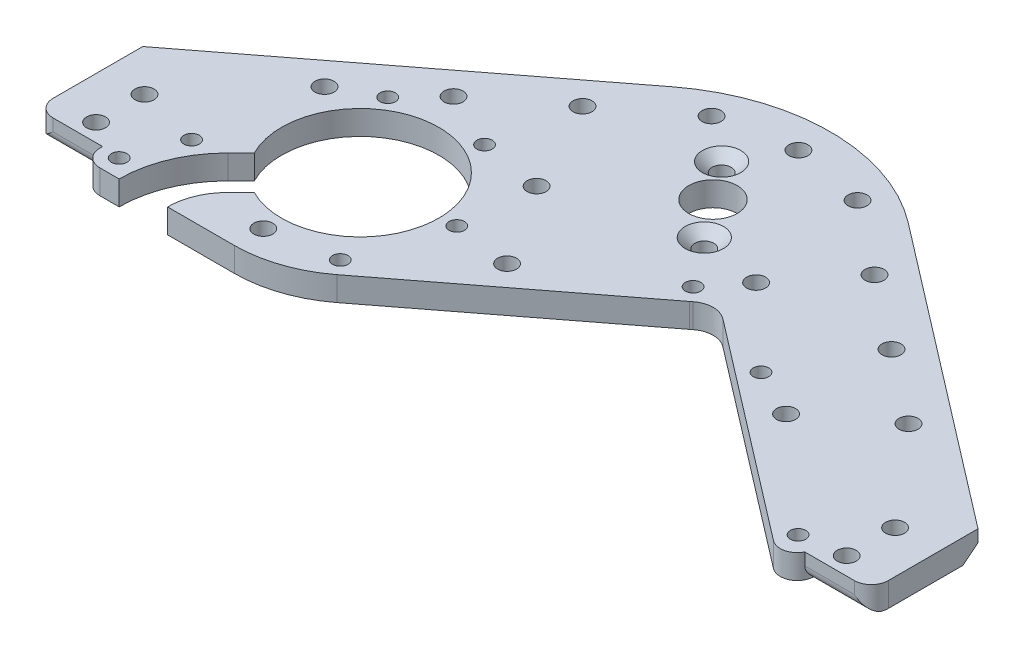
SolidWorks part; units mm, degrees
material "Alum Plate"
ref_plane "Front Plane" through (0, 0, 0) normal (0, 0, 1) x (1, 0, 0)
ref_plane "Top Plane" through (0, 0, 0) normal (0, 1, 0) x (1, 0, 0)
ref_plane "Right Plane" through (0, 0, 0) normal (1, 0, 0) x (0, 0, -1)
sketch "Top Layout" plane through (0, 0, 0) normal (0, 1, 0) x (1, 0, 0)
  line L0 (-114.046, -123.825) -> (-104.775, -123.825) construction
  line L1 (-104.775, -142.875) -> (-101.6, -142.875)
  line L2 (-104.775, -142.875) -> (-104.775, -104.775)
  line L3 (-104.775, -104.775) -> (-101.6, -104.775)
  line L4 (-101.6, -142.875) -> (-101.6, -104.775)
  line L5 (-104.775, -142.875) -> (-101.6, -104.775) construction
  line L6 (-104.775, -104.775) -> (-101.6, -142.875) construction
  line L7 (-19.05, -105.8164) -> (-101.6, -105.8164)
  line L8 (-19.05, -105.8164) -> (-19.05, -141.8336)
  line L9 (-19.05, -141.8336) -> (-101.6, -141.8336)
  line L10 (-101.6, -105.8164) -> (-101.6, -141.8336)
  line L11 (-19.05, -105.8164) -> (-101.6, -141.8336) construction
  line L12 (-19.05, -141.8336) -> (-101.6, -105.8164) construction
  line L13 (-133.096, -85.725) -> (-114.046, -85.725)
  line L14 (-133.096, -85.725) -> (-133.096, -161.925)
  line L15 (-133.096, -161.925) -> (-114.046, -161.925)
  line L16 (-114.046, -85.725) -> (-114.046, -161.925)
  line L17 (-133.096, -85.725) -> (-114.046, -161.925) construction
  line L18 (-133.096, -161.925) -> (-114.046, -85.725) construction
  line L19 (-104.775, -123.825) -> (0, -123.825) construction
  line L20 (0, -123.825) -> (0, 0) construction
  line L21 (-52.3528, -40.1717) -> (0, 0) construction
  line L22 (-70.6449, -16.3328) -> (-18.2922, 23.8388)
  line L23 (-34.0606, -64.0105) -> (18.2922, -23.8388)
  line L24 (-30.9251, 40.3023) -> (-122.2248, -29.7544)
  line L25 (-153.9748, -53.975) -> (-153.9748, -123.825)
  line L26 (-109.5248, -162.052) -> (109.5248, -162.052)
  line L27 (0, -162.052) -> (0, -123.825) construction
  line L28 (-109.5248, -162.052) -> (-109.5248, -20.0093) construction
  line L29 (-104.775, -142.875) -> (-104.775, -152.527)
  line L30 (-104.775, -152.527) -> (104.775, -152.527)
  line L31 (104.775, -104.775) -> (101.6, -104.775)
  line L32 (-144.4498, -73.025) -> (-109.5248, -73.025)
  line L33 (-144.4498, -73.025) -> (-144.4498, -123.825)
  line L34 (-144.4498, -123.825) -> (-109.5248, -123.825) construction
  line L35 (-109.5248, -73.025) -> (-109.5248, -162.052)
  line L36 (-144.4498, -73.025) -> (-109.5248, -123.825) construction
  line L37 (-144.4498, -123.825) -> (-109.5248, -73.025) construction
  line L38 (101.6, -142.875) -> (101.6, -104.775)
  line L39 (104.775, -142.875) -> (101.6, -142.875)
  line L40 (104.775, -142.875) -> (104.775, -104.775)
  line L41 (104.775, -142.875) -> (104.775, -152.527)
  line L42 (109.5248, -162.052) -> (109.5248, -20.0093) construction
  line L43 (30.9251, 40.3023) -> (122.2248, -29.7544)
  line L45 (19.05, -141.8336) -> (101.6, -141.8336)
  line L46 (101.6, -105.8164) -> (101.6, -141.8336)
  line L47 (19.05, -105.8164) -> (101.6, -105.8164)
  line L48 (19.05, -105.8164) -> (19.05, -141.8336)
  line L49 (133.096, -161.925) -> (114.046, -161.925)
  line L50 (114.046, -85.725) -> (114.046, -161.925)
  line L51 (133.096, -85.725) -> (114.046, -85.725)
  line L52 (133.096, -85.725) -> (133.096, -161.925)
  line L53 (144.4498, -123.825) -> (109.5248, -123.825) construction
  line L54 (109.5248, -73.025) -> (109.5248, -162.052)
  line L55 (144.4498, -73.025) -> (109.5248, -73.025)
  line L56 (144.4498, -73.025) -> (144.4498, -123.825)
  line L57 (-109.5248, -123.825) -> (-109.5248, -162.052) construction
  line L62 (-153.9748, -53.975) -> (-122.2248, -53.975)
  line L63 (-122.2248, -53.975) -> (-122.2248, -29.7544)
  line L64 (-144.4498, -123.825) -> (-153.9748, -123.825)
  line L65 (153.9748, -53.975) -> (153.9748, -123.825)
  line L66 (109.5248, -123.825) -> (109.5248, -162.052) construction
  line L67 (144.4498, -123.825) -> (153.9748, -123.825)
  line L68 (122.2248, -29.7544) -> (122.2248, -53.975)
  line L73 (-104.775, -104.775) -> (-104.775, -16.3647) construction
  line L74 (-95.25, -162.052) -> (-95.25, -9.0559) construction
  line L75 (-109.5248, -162.052) -> (-109.5248, -123.825) construction
  line L76 (109.5248, -162.052) -> (109.5248, -123.825) construction
  line L77 (122.2248, -53.975) -> (153.9748, -53.975)
  line L83 (104.775, -155.5496) -> (-104.775, -155.5496) construction
  line L88 (95.25, -162.052) -> (95.25, -9.0559) construction
  line L89 (104.775, -104.775) -> (104.775, -16.3647) construction
  line L92 (-104.775, -152.527) -> (-104.775, -162.052) construction
  line L93 (-14.605, -76.327) -> (14.605, -76.327)
  line L94 (-14.605, -76.327) -> (-14.605, -152.527)
  line L95 (-14.605, -152.527) -> (14.605, -152.527)
  line L96 (14.605, -76.327) -> (14.605, -152.527)
  line L97 (-14.605, -76.327) -> (14.605, -152.527) construction
  line L98 (-14.605, -152.527) -> (14.605, -76.327) construction
  line L99 (104.775, -152.527) -> (104.775, -162.052) construction
  line L100 (-19.05, -105.8164) -> (0, -105.8164) construction
  line L107 (0, -105.8164) -> (19.05, -105.8164) construction
  line L108 (104.775, -123.825) -> (114.046, -123.825) construction
  circle A0 centre (0, 0) radius 114.3
  circle A1 centre (0, 0) radius 6.35
  circle A2 centre (-52.3528, -40.1717) radius 17.8
  circle A3 centre (0, 0) radius 30.0482
  circle A4 centre (-52.3528, -40.1717) radius 30.0482
  arc A5 (-30.9251, 40.3023) -> (30.9251, 40.3023) centre (0, 0) cw
  point P2 (-103.1875, -123.825)
  point P7 (-60.325, -123.825)
  point P12 (-123.571, -123.825)
  point P30 (-126.9873, -98.425)
  point P35 (0, -114.427)
  point P53 (0, -152.527)
  dimension "D1" = 35.6
  dimension "D2" = 12.7
  dimension "D3" = 228.6
  dimension "D11" = 60.0964
  dimension "D12" = 50.8
  dimension "D14" = 52.5
  dimension "D4" = 3.175
  dimension "D5" = 19.05
  dimension "D6" = 76.2
  dimension "D7" = 82.55
  dimension "D8" = 38.1
  dimension "D9" = 104.775
  dimension "D10" = 18.0086
  dimension "D13" = 9.525
  dimension "D15" = 4.7498
  dimension "D16" = 9.525
  dimension "D17" = 9.652
  dimension "D18" = 50.8
  dimension "D19" = 12.446
  dimension "D20" = 65.9892
  dimension "D21" = 19.05
  dimension "D22" = 34.925
  dimension "D23" = 123.825
  dimension "D24" = 12.7
  dimension "D25" = 9.525
  dimension "D26" = 29.21
  dimension "D27" = 76.2
  dimension "D28" = 3.0226
sketch "Side Layout" plane through (0, 0, 0) normal (1, 0, 0) x (0, 0, -1)
  line L0 (0, -38.1) -> (0, 33.7344) construction
  line L1 (-114.3, -20.955) -> (114.3, -20.955)
  line L2 (-114.3, -20.955) -> (-114.3, -33.655)
  line L3 (-114.3, -33.655) -> (114.3, -33.655)
  line L4 (114.3, -20.955) -> (114.3, -33.655)
  line L5 (-114.3, -20.955) -> (114.3, -33.655) construction
  line L6 (-114.3, -33.655) -> (114.3, -20.955) construction
  line L7 (-9.525, -32.9406) -> (9.525, -32.9406)
  line L8 (-9.525, -32.9406) -> (-9.525, -38.1)
  line L9 (-9.525, -38.1) -> (9.525, -38.1)
  line L10 (9.525, -32.9406) -> (9.525, -38.1)
  line L11 (-9.525, -32.9406) -> (9.525, -38.1) construction
  line L12 (-9.525, -38.1) -> (9.525, -32.9406) construction
  line L13 (-11.9126, -29.3338) -> (11.9126, -29.3338)
  line L14 (-11.9126, -29.3338) -> (-11.9126, -32.9406)
  line L15 (-11.9126, -32.9406) -> (11.9126, -32.9406)
  line L16 (11.9126, -29.3338) -> (11.9126, -32.9406)
  line L17 (-11.9126, -29.3338) -> (11.9126, -32.9406) construction
  line L18 (-11.9126, -32.9406) -> (11.9126, -29.3338) construction
  line L19 (-6.35, -32.9406) -> (6.35, -32.9406)
  line L20 (-6.35, -32.9406) -> (-6.35, 33.7344)
  line L21 (-6.35, 33.7344) -> (6.35, 33.7344)
  line L22 (6.35, -32.9406) -> (6.35, 33.7344)
  line L23 (-6.35, -32.9406) -> (6.35, 33.7344) construction
  line L24 (-6.35, 33.7344) -> (6.35, -32.9406) construction
  line L25 (-162.052, 0) -> (-123.825, 0) construction
  line L26 (114.3, -33.655) -> (114.3, 0) construction
  line L27 (-142.875, 19.05) -> (-104.775, 19.05)
  line L28 (-40.1717, -9.525) -> (-40.1717, 5.4) construction
  line L29 (-142.875, 19.05) -> (-142.875, -19.05)
  line L30 (-142.875, -19.05) -> (-104.775, -19.05)
  line L31 (-104.775, 19.05) -> (-104.775, -19.05)
  line L32 (-142.875, 19.05) -> (-104.775, -19.05) construction
  line L33 (-142.875, -19.05) -> (-104.775, 19.05) construction
  line L34 (-130.175, -38.1) -> (-117.9516, -38.1) construction
  line L35 (-57.9717, -14.6) -> (-22.3717, -14.6)
  line L36 (-30.0482, -2.794) -> (30.0482, -2.794)
  line L37 (-30.0482, -2.794) -> (-30.0482, -20.955)
  line L38 (-30.0482, -20.955) -> (30.0482, -20.955)
  line L39 (30.0482, -2.794) -> (30.0482, -20.955)
  line L40 (-30.0482, -2.794) -> (30.0482, -20.955) construction
  line L41 (-30.0482, -20.955) -> (30.0482, -2.794) construction
  line L42 (-30.0482, -2.794) -> (-30.0482, 0) construction
  line L43 (-123.825, 0) -> (0, 0) construction
  line L44 (-57.9717, -14.6) -> (-57.9717, 25.4)
  line L45 (-57.9717, 25.4) -> (-22.3717, 25.4)
  line L46 (-22.3717, -14.6) -> (-22.3717, 25.4)
  line L47 (-19.05, 0) -> (19.05, 0)
  line L48 (-19.05, 0) -> (-19.05, -1.9812)
  line L49 (-19.05, -1.9812) -> (19.05, -1.9812)
  line L50 (19.05, 0) -> (19.05, -1.9812)
  line L51 (-19.05, 0) -> (19.05, -1.9812) construction
  line L52 (-19.05, -1.9812) -> (19.05, 0) construction
  line L53 (-70.2199, -3.175) -> (-10.1235, -3.175)
  line L54 (-70.2199, -3.175) -> (-70.2199, -15.875)
  line L55 (-70.2199, -15.875) -> (-10.1235, -15.875)
  line L56 (-10.1235, -3.175) -> (-10.1235, -15.875)
  line L57 (-70.2199, -3.175) -> (-10.1235, -15.875) construction
  line L58 (-70.2199, -15.875) -> (-10.1235, -3.175) construction
  line L59 (-40.1717, -9.525) -> (-40.1717, 0) construction
  line L60 (-57.9717, -14.6) -> (-22.3717, 25.4) construction
  line L61 (-57.9717, 25.4) -> (-22.3717, -14.6) construction
  line L62 (-22.3717, 0) -> (-57.9717, 0) construction
  line L63 (-137.8162, 0) -> (-123.825, -13.9912) construction
  line L64 (-139.065, 15.24) -> (-108.585, 15.24) construction
  line L65 (-139.065, 15.24) -> (-139.065, -15.24) construction
  line L66 (-139.065, -15.24) -> (-108.585, -15.24) construction
  line L67 (-108.585, 15.24) -> (-108.585, -15.24) construction
  line L68 (-139.065, 15.24) -> (-108.585, -15.24) construction
  line L69 (-139.065, -15.24) -> (-108.585, 15.24) construction
  line L70 (-137.8162, 0) -> (-123.825, 13.9912) construction
  line L71 (-123.825, -13.9912) -> (-109.8338, 0) construction
  line L72 (-123.825, 13.9912) -> (-109.8338, 0) construction
  line L73 (-137.8162, 0) -> (-109.8338, 0) construction
  line L74 (-123.825, -13.9912) -> (-123.825, 13.9912) construction
  line L75 (-6.35, 17.8594) -> (6.35, 17.8594)
  line L76 (114.3, 0) -> (-114.3, 0) construction
  line L77 (-22.3717, 19.05) -> (-6.35, 19.05) construction
  line L78 (-123.825, 38.1) -> (-97.9206, 38.1) construction
  line L79 (-19.05, -3.5814) -> (19.05, -3.5814)
  line L80 (-19.05, -3.5814) -> (-19.05, -1.9812)
  line L81 (-19.05, -1.9812) -> (19.05, -1.9812)
  line L82 (19.05, -3.5814) -> (19.05, -1.9812)
  line L83 (-19.05, -3.5814) -> (19.05, -1.9812) construction
  line L84 (-19.05, -1.9812) -> (19.05, -3.5814) construction
  line L85 (-8.7376, -16.7608) -> (8.7376, -16.7608)
  line L86 (-8.7376, -16.7608) -> (-8.7376, -29.3338)
  line L87 (-8.7376, -29.3338) -> (8.7376, -29.3338)
  line L88 (8.7376, -16.7608) -> (8.7376, -29.3338)
  line L89 (-8.7376, -16.7608) -> (8.7376, -29.3338) construction
  line L90 (-8.7376, -29.3338) -> (8.7376, -16.7608) construction
  line L91 (-8.7376, -3.5814) -> (8.7376, -3.5814)
  line L92 (-8.7376, -3.5814) -> (-8.7376, -16.1544)
  line L93 (-8.7376, -16.1544) -> (8.7376, -16.1544)
  line L94 (8.7376, -3.5814) -> (8.7376, -16.1544)
  line L95 (-8.7376, -3.5814) -> (8.7376, -16.1544) construction
  line L96 (-8.7376, -16.1544) -> (8.7376, -3.5814) construction
  circle A0 centre (-123.825, 0) radius 18.0086
  circle A1 centre (-123.825, 0) radius 38.1
  circle A2 centre (-139.065, 15.24) radius 1.905
  circle A3 centre (-108.585, 15.24) radius 1.905
  circle A4 centre (-108.585, -15.24) radius 1.905
  circle A5 centre (-139.065, -15.24) radius 1.905
  circle A6 centre (-137.8162, 0) radius 1.6002
  circle A7 centre (-123.825, 13.9912) radius 1.6002
  circle A8 centre (-109.8338, 0) radius 1.6002
  circle A9 centre (-123.825, -13.9912) radius 1.6002
  point P0 (0, -27.305)
  point P6 (0, -31.1372)
  point P7 (0, -35.5203)
  point P21 (0, 0.3969)
  point P32 (0, -11.8745)
  point P43 (0, -0.9906)
  point P55 (-40.1717, -9.525)
  point P72 (-40.1717, 5.4)
  point P88 (0, -23.0473)
  point P93 (0, -2.7813)
  point P102 (0, -9.8679)
  dimension "D17" = 3.81
  dimension "D18" = 3.2004
  dimension "D1" = 12.7
  dimension "D2" = 5.1594
  dimension "D3" = 19.05
  dimension "D4" = 3.6068
  dimension "D5" = 23.8252
  dimension "D6" = 12.7
  dimension "D7" = 18.161
  dimension "D8" = 1.9812
  dimension "D9" = 12.7
  dimension "D10" = 40
  dimension "D11" = 25.4
  dimension "D12" = 50.8
  dimension "D13" = 41.275
  dimension "D14" = 30.48
  dimension "D15" = 4.445
  dimension "D16" = 19.7866
  dimension "D19" = 15.875
  dimension "D20" = 6.35
  dimension "D21" = 38.1
  dimension "D22" = 1.6002
  dimension "D23" = 38.1
  dimension "D24" = 17.4752
  dimension "D25" = 12.573
ref_plane "Plane1" through (0, 25.4, 0) normal (0, 1, 0) x (1, 0, 0)
sketch "Sketch3" plane through (0, 25.4, 0) normal (0, 1, 0) x (1, 0, 0)
  line L0 (-104.775, -36.3747) -> (-30.9251, 20.2924)
  line L1 (-104.775, -104.775) -> (-104.775, -16.3647) construction
  line L2 (0, -200130.175) -> (0, 199882.0484) construction
  line L3 (-30.9251, 40.3023) -> (-122.2248, -29.7544) construction
  line L5 (-104.775, -36.3747) -> (-104.775, -77.6497)
  line L6 (-92.075, -77.6497) -> (-104.775, -77.6497)
  line L7 (30.9251, 20.2924) -> (104.775, -36.3747)
  line L8 (104.775, -77.6497) -> (92.075, -77.6497)
  line L9 (104.775, -36.3747) -> (104.775, -77.6497)
  line L11 (104.775, -104.775) -> (104.775, -16.3647) construction
  line L12 (30.9251, 40.3023) -> (122.2248, -29.7544) construction
  line L13 (92.075, -74.6536) -> (24.1423, -22.5271)
  line L14 (-32.2514, -66.3682) -> (20.1013, -26.1965)
  line L15 (-30.9251, 20.2924) -> (0, 44.022)
  line L16 (0, 44.022) -> (30.9251, 20.2924)
  line L17 (-92.075, -77.6497) -> (-92.075, -73.1917)
  line L19 (-92.075, -73.1917) -> (-52.3528, -73.1917)
  line L20 (92.075, -74.6536) -> (92.075, -77.6497)
  circle A1 centre (-52.3528, -40.1717) radius 20.6375
  circle A2 centre (0, 0) radius 6.35
  circle A3 centre (0, 0) radius 6.35 construction
  arc A4 (-52.3528, -73.1917) -> (-32.2514, -66.3682) centre (-52.3528, -40.1717) ccw
  arc A5 (20.1013, -26.1965) -> (24.1423, -22.5271) centre (0, 0) ccw
  arc A6 (30.9251, 20.2924) -> (-30.9251, 20.2924) centre (0, -20.01) ccw construction
  point P28 (0, 44.022)
  dimension "D1" = 33.02
  dimension "D5" = 50.8
  dimension "D7" = 41.275
  dimension "D2" = 41.275
  dimension "D3" = 34.925
  dimension "D4" = 12.7
  dimension "D6" = 38.1
extrude "Boss-Extrude1" add sketch "Sketch3" against normal blind 6.35
ref_plane "Plane3" through (-104.775, 0, 0) normal (-1, 0, 0) x (0, 0, 1)
sketch "Sketch6" plane through (-104.775, 0, 0) normal (-1, 0, 0) x (0, 0, 1)
  line L0 (162.052, -25.4) -> (162.052, 25.4)
  line L1 (162.052, 25.4) -> (77.6497, 25.4)
  line L2 (36.3747, 25.4) -> (77.6497, 25.4) construction
  line L3 (147.7645, 11.1125) -> (162.052, 11.1125) construction
  line L4 (162.052, 0) -> (71.2997, 0) construction
  line L5 (77.6497, 25.4) -> (77.6497, 19.05)
  line L6 (77.6497, 19.05) -> (36.3747, 19.05)
  line L7 (36.3747, 19.05) -> (36.3747, 6.35)
  line L8 (36.3747, 6.35) -> (71.2997, 6.35)
  line L10 (99.6315, -3.175) -> (99.6315, 11.1125) construction
  line L11 (71.2997, -25.4) -> (162.052, -25.4)
  line L13 (71.2997, 6.35) -> (71.2997, -25.4)
  line L14 (152.527, -25.4) -> (152.527, 25.4) construction
  line L15 (99.6315, 11.1125) -> (99.6315, 25.4) construction
  line L16 (147.7645, 11.1125) -> (147.7645, 25.4) construction
  line L17 (94.869, -7.9375) -> (104.394, -7.9375) construction
  line L18 (94.869, -7.9375) -> (94.869, 25.4) construction
  line L19 (94.869, 25.4) -> (104.394, 25.4) construction
  line L20 (104.394, -7.9375) -> (104.394, 25.4) construction
  line L21 (94.869, -7.9375) -> (104.394, 25.4) construction
  line L22 (94.869, 25.4) -> (104.394, -7.9375) construction
  line L23 (147.7645, 11.1125) -> (147.7645, -3.175) construction
  line L24 (104.394, -7.9375) -> (123.825, -7.9375) construction
  line L25 (143.002, -7.9375) -> (152.527, -7.9375) construction
  line L26 (143.002, -7.9375) -> (143.002, 25.4) construction
  line L27 (143.002, 25.4) -> (152.527, 25.4) construction
  line L28 (152.527, -7.9375) -> (152.527, 25.4) construction
  line L29 (143.002, -7.9375) -> (152.527, 25.4) construction
  line L30 (143.002, 25.4) -> (152.527, -7.9375) construction
  line L31 (123.825, -7.9375) -> (152.527, -7.9375) construction
  line L32 (104.775, 19.05) -> (104.775, -19.05) construction
  line L34 (155.702, -25.4) -> (155.702, 25.4) construction
  circle A0 centre (109.8338, 0) radius 1.6002 construction
  circle A1 centre (123.825, 13.9912) radius 1.6002 construction
  circle A2 centre (137.8162, 0) radius 1.6002 construction
  circle A3 centre (123.825, -13.9912) radius 1.6002 construction
  circle A4 centre (109.8338, 0) radius 1.6002 construction
  circle A5 centre (123.825, 13.9912) radius 1.6002 construction
  circle A6 centre (137.8162, 0) radius 1.6002 construction
  circle A7 centre (123.825, -13.9912) radius 1.6002 construction
  circle A8 centre (123.825, 0) radius 18.0086 construction
  circle A9 centre (123.825, 0) radius 18.0086 construction
  circle A10 centre (123.825, 0) radius 9.525
  circle A11 centre (108.585, -15.24) radius 1.905 construction
  circle A12 centre (108.585, 15.24) radius 1.905 construction
  circle A13 centre (139.065, 15.24) radius 1.905 construction
  circle A14 centre (139.065, -15.24) radius 1.905 construction
  circle A15 centre (108.585, -15.24) radius 1.905
  circle A16 centre (108.585, 15.24) radius 1.905
  circle A17 centre (139.065, 15.24) radius 1.905
  circle A18 centre (139.065, -15.24) radius 1.905
  circle A19 centre (147.7645, 11.1125) radius 2.5527
  circle A26 centre (99.6315, 11.1125) radius 2.5527
  circle A27 centre (99.6315, -3.175) radius 2.5527
  circle A28 centre (147.7645, -3.175) radius 2.5527
  point P29 (0, 0)
  point P55 (99.6315, 8.7312)
  point P61 (147.7645, 8.7312)
  dimension "D4" = 19.05
  dimension "D7" = 5.1054
  dimension "D1" = 6.35
  dimension "D2" = 12.7
  dimension "D3" = 25.4
  dimension "D5" = 6.35
  dimension "D6" = 3.175
  dimension "D8" = 0.381
  dimension "D9" = 14.2875
  dimension "D10" = 9.525
  dimension "D12" = 33.3375
sketch "Sketch12" [suppressed] plane through (0, 19.05, 0) normal (0, 1, 0) x (1, 0, 0)
  line L0 (-104.775, -77.6497) -> (-104.775, -36.3747)
  line L1 (-104.775, -36.3747) -> (-92.075, -36.3747)
  line L3 (-92.075, -36.3747) -> (-92.075, -77.6497)
  line L5 (-92.075, -77.6497) -> (-104.775, -77.6497)
  line L6 (-98.425, -77.6497) -> (-98.425, -63.3622) construction
  line L7 (-98.425, -63.3622) -> (-98.425, -50.6622) construction
  line L8 (-98.425, -50.6622) -> (-98.425, -36.3747) construction
  line L10 (-98.425, -36.3747) -> (-104.775, -36.3747) construction
  circle A0 centre (-98.425, -63.3622) radius 2.5527
  circle A1 centre (-98.425, -50.6622) radius 2.5527
  dimension "D2" = 5.1054
  dimension "D1" = 12.7
  dimension "D3" = 12.7
sketch "Sketch8" plane through (0, 25.4, 0) normal (0, 1, 0) x (1, 0, 0)
  line L0 (-109.5248, -162.052) -> (-109.5248, -20.0093) construction
  line L1 (-104.775, -77.6497) -> (-109.5248, -77.6497)
  line L2 (-104.775, -77.6497) -> (-104.775, -36.3747)
  line L3 (-104.775, -36.3747) -> (-109.5248, -36.3747)
  line L4 (-109.5248, -77.6497) -> (-109.5248, -36.3747)
  line L5 (-104.775, -77.6497) -> (-109.5248, -36.3747) construction
  line L6 (-104.775, -36.3747) -> (-109.5248, -77.6497) construction
  line L7 (104.775, -77.6497) -> (109.5248, -77.6497)
  line L8 (104.775, -77.6497) -> (104.775, -36.3747)
  line L9 (104.775, -36.3747) -> (109.5248, -36.3747)
  line L10 (109.5248, -77.6497) -> (109.5248, -36.3747)
  line L11 (104.775, -77.6497) -> (109.5248, -36.3747) construction
  line L12 (104.775, -36.3747) -> (109.5248, -77.6497) construction
  point P4 (-107.1499, -57.0122)
  point P10 (107.1499, -57.0122)
extrude "Boss-Extrude4" add sketch "Sketch8" against normal through all
sketch "Sketch9" plane through (0, 25.4, 0) normal (0, 1, 0) x (1, 0, 0)
  line L0 (7.4916, -9.7632) -> (0, 0) construction
  line L1 (0, 0) -> (-7.4916, 9.7632) construction
  line L2 (0, 44.022) -> (-104.775, -36.3747) construction
  circle A0 centre (-7.4916, 9.7632) radius 2.4892
  circle A1 centre (7.4916, -9.7632) radius 2.4892
  dimension "D2" = 4.9784
  dimension "D1" = 24.6126
extrude "Collar Holes" cut sketch "Sketch9" against normal through all
sketch "Sketch10" plane through (0, 25.4, 0) normal (0, 1, 0) x (1, 0, 0)
  line L0 (0, 33.4567) -> (0, 30.79) construction
  line L1 (-5.1026, 40.1066) -> (0, 33.4567) construction
  line L2 (0, 33.4567) -> (5.1026, 40.1066) construction
  line L3 (0, 44.022) -> (-104.775, -36.3747) construction
  line L4 (104.775, -36.3747) -> (0, 44.022) construction
  circle A0 centre (0, 33.4567) radius 4.7625 construction
  circle A1 centre (0, 33.4567) radius 2.0193
  arc A3 (30.9251, 20.2924) -> (-30.9251, 20.2924) centre (0, -20.01) ccw construction
  dimension "D2" = 9.525
  dimension "D3" = 4.0386
  dimension "D1" = 8.382
extrude "Spacer Holes" cut sketch "Sketch10" against normal through all
pattern_linear "Spacer Hole Pattern" count 5 spacing 24.13 along (-0.7934, 0, 0.6088) of "Spacer Holes"
mirror "Spacer Hole Mirror" about plane through (0, 0, 0) normal (1, 0, 0) of "Spacer Hole Pattern"
sketch "Sketch16" plane through (0, 25.4, 0) normal (0, 1, 0) x (1, 0, 0)
  line L0 (-109.5248, -50.6622) -> (-98.425, -50.6622) construction
  line L1 (-109.5248, -36.3747) -> (-109.5248, -77.6497) construction
  line L2 (-98.425, -50.6622) -> (-98.425, -63.3622) construction
  line L3 (-98.425, -63.3622) -> (-109.5248, -63.3622) construction
  line L4 (-98.425, -63.3622) -> (-98.425, -77.6497) construction
  line L5 (-109.5248, -77.6497) -> (-92.075, -77.6497) construction
  line L6 (-98.425, -50.6622) -> (-98.425, -36.3747) construction
  line L7 (-104.775, -36.3747) -> (-109.5248, -36.3747) construction
  line L8 (-104.775, -36.3747) -> (-104.775, -77.6497) construction
  line L9 (0, 0) -> (0, 30.79) construction
  line L10 (104.775, -36.3747) -> (104.775, -77.6497) construction
  circle A0 centre (-98.425, -50.6622) radius 2.0193
  circle A1 centre (-98.425, -63.3622) radius 2.0193
  circle A4 centre (98.425, -63.3622) radius 2.0193
  circle A5 centre (98.425, -50.6622) radius 2.0193
  arc A6 (30.9251, 20.2924) -> (-30.9251, 20.2924) centre (0, -20.01) ccw construction
  dimension "D1" = 4.0386
  dimension "D2" = 12.7
  dimension "D3" = 6.35
extrude "Custom Nutstrip Holes" cut sketch "Sketch16" against normal through all
sketch "Sketch36" plane through (0, 25.4, 0) normal (0, 1, 0) x (1, 0, 0)
  line L0 (-52.3528, -65.5717) -> (-12.44, -41.5615) construction
  line L1 (-12.44, -41.5615) -> (24.5129, -13.2066) construction
  line L2 (24.5129, -13.2066) -> (58.2939, -39.1277) construction
  line L3 (-32.2514, -66.3682) -> (20.1013, -26.1965) construction
  line L4 (24.1423, -22.5271) -> (92.075, -74.6536) construction
  line L5 (-12.44, -41.5615) -> (-7.8012, -47.6069) construction
  line L6 (58.2939, -39.1277) -> (53.6552, -45.1731) construction
  line L7 (-52.3528, -65.5717) -> (-52.3528, -40.1717) construction
  line L8 (58.2939, -39.1277) -> (92.075, -65.0488) construction
  line L9 (92.075, -65.0488) -> (92.075, -77.6497) construction
  line L10 (-52.3528, -40.1717) -> (-26.1764, -20.0858) construction
  line L11 (-26.1764, -20.0858) -> (0, 0) construction
  line L12 (92.075, -74.6536) -> (92.075, -77.6497) construction
  circle A0 centre (-52.3528, -65.5717) radius 2.0193
  circle A1 centre (58.2939, -39.1277) radius 2.0193
  circle A2 centre (24.5129, -13.2066) radius 2.0193
  circle A3 centre (-12.44, -41.5615) radius 2.0193
  circle A4 centre (-76.5745, -25.3009) radius 2.0193 construction
  circle A5 centre (-52.3528, -65.5717) radius 4.7625 construction
  circle A6 centre (-12.44, -41.5615) radius 4.7625 construction
  circle A7 centre (24.5129, -13.2066) radius 4.7625 construction
  circle A8 centre (58.2939, -39.1277) radius 4.7625 construction
  arc A9 (-52.3528, -73.1917) -> (-32.2514, -66.3682) centre (-52.3528, -40.1717) ccw construction
  circle A10 centre (-26.1764, -20.0858) radius 2.0193
  dimension "D1" = 9.525
  dimension "D2" = 25.4
  dimension "D3" = 7.62
extrude "Aux Spacer Holes" cut sketch "Sketch36" against normal through all
sketch "Sketch38" [suppressed] plane through (-104.775, 0, 0) normal (-1, 0, 0) x (0, 0, 1)
  line L1 (152.527, -7.9375) -> (143.002, -7.9375)
  line L2 (152.527, -7.9375) -> (152.527, 25.4)
  line L3 (152.527, 25.4) -> (143.002, 25.4)
  line L4 (143.002, -7.9375) -> (143.002, 25.4)
  line L5 (152.527, -7.9375) -> (143.002, 25.4) construction
  line L6 (152.527, 25.4) -> (143.002, -7.9375) construction
  point P4 (147.7645, 8.7312)
extrude "Cut-Extrude16" [suppressed] cut sketch "Sketch38" against normal blind 9.525
sketch "Sketch46" [suppressed] plane through (-104.775, 0, 0) normal (-1, 0, 0) x (0, 0, 1)
  line L0 (142.875, 19.05) -> (104.775, -19.05) construction
  line L1 (104.14, 19.685) -> (143.51, 19.685)
  line L2 (104.14, 19.685) -> (104.14, -19.685)
  line L3 (104.14, -19.685) -> (143.51, -19.685)
  line L4 (143.51, 19.685) -> (143.51, -19.685)
  line L5 (104.14, 19.685) -> (143.51, -19.685) construction
  line L6 (104.14, -19.685) -> (143.51, 19.685) construction
  point P0 (123.825, 0)
  dimension "D1" = 39.37
extrude "Cut-Extrude21" [suppressed] cut sketch "Sketch46" against normal blind 6.985
ref_plane "Plane5" through (0, 0, 152.527) normal (0, 0, 1) x (1, 0, 0)
sketch "Sketch41" plane through (0, 0, 152.527) normal (0, 0, 1) x (1, 0, 0)
  line L0 (-104.775, -7.9375) -> (-104.775, 25.4) construction
  line L1 (-104.775, -7.9375) -> (-104.775, 12.7)
  line L2 (-104.775, -7.9375) -> (104.775, -7.9375)
  line L3 (104.775, -7.9375) -> (104.775, 12.7)
  line L4 (104.775, 25.4) -> (-104.775, 25.4)
  line L5 (0, -7.9375) -> (0, 25.4) construction
  line L6 (-104.775, 3.9624) -> (-100.0125, 3.9624) construction
  line L7 (-100.0125, 3.9624) -> (-100.0125, 25.4) construction
  line L8 (104.775, 3.9624) -> (100.0125, 3.9624) construction
  line L9 (100.0125, 3.9624) -> (100.0125, 25.4) construction
  line L10 (19.05, 20.6375) -> (23.8252, 20.6375) construction
  line L11 (19.05, 15.875) -> (78.5876, 15.875) construction
  line L12 (19.05, 15.875) -> (19.05, 25.4) construction
  line L13 (19.05, 25.4) -> (78.5876, 25.4) construction
  line L14 (78.5876, 15.875) -> (78.5876, 25.4) construction
  line L15 (19.05, 15.875) -> (78.5876, 25.4) construction
  line L16 (19.05, 25.4) -> (78.5876, 15.875) construction
  line L17 (23.8252, 20.6375) -> (38.1127, 20.6375) construction
  line L18 (38.1127, 20.6375) -> (52.4002, 20.6375) construction
  line L19 (52.4002, 20.6375) -> (66.6877, 20.6375) construction
  line L20 (-104.775, 25.4) -> (-112.395, 25.4)
  line L21 (-112.395, 25.4) -> (-112.395, 3.175)
  line L22 (-112.395, 3.175) -> (-109.5248, 3.175)
  line L23 (-109.5248, 3.175) -> (-109.5248, 12.7)
  line L24 (-109.5248, 12.7) -> (-104.775, 12.7)
  line L25 (-104.775, 12.7) -> (-104.775, 25.4) construction
  line L26 (104.775, 25.4) -> (112.395, 25.4)
  line L27 (112.395, 25.4) -> (112.395, 3.175)
  line L28 (112.395, 3.175) -> (109.5248, 3.175)
  line L29 (109.5248, 3.175) -> (109.5248, 12.7)
  line L30 (109.5248, 12.7) -> (104.775, 12.7)
  line L31 (104.775, 12.7) -> (104.775, 25.4) construction
  line L32 (-100.0125, 3.9624) -> (-87.3125, 3.9624) construction
  line L33 (-63.5, -1.5875) -> (0, -1.5875) construction
  line L34 (0, -1.5875) -> (63.5, -1.5875) construction
  line L35 (63.5, -1.5875) -> (63.5, -7.9375) construction
  circle A0 centre (-100.0125, 3.9624) radius 2.5527
  circle A1 centre (100.0125, 3.9624) radius 2.5527
  circle A2 centre (23.8252, 20.6375) radius 2.5527
  circle A3 centre (38.1127, 20.6375) radius 2.5527
  circle A4 centre (52.4002, 20.6375) radius 2.5527
  circle A5 centre (66.6877, 20.6375) radius 2.5527
  circle A6 centre (-66.6877, 20.6375) radius 2.5527
  circle A7 centre (-52.4002, 20.6375) radius 2.5527
  circle A8 centre (-38.1127, 20.6375) radius 2.5527
  circle A9 centre (-23.8252, 20.6375) radius 2.5527
  circle A10 centre (-87.3125, 3.9624) radius 2.5527
  circle A11 centre (87.3125, 3.9624) radius 2.5527
  circle A12 centre (-63.5, -1.5875) radius 2.5527
  circle A13 centre (63.5, -1.5875) radius 2.5527
  point P14 (48.8188, 20.6375)
  dimension "D3" = 5.1054
  dimension "D7" = 5.1054
  dimension "D1" = 21.4376
  dimension "D2" = 4.7625
  dimension "D4" = 9.525
  dimension "D5" = 59.5376
  dimension "D6" = 4.7752
  dimension "D8" = 14.2875
  dimension "D9" = 7.62
  dimension "D10" = 4.7498
  dimension "D11" = 12.7
  dimension "D12" = 9.525
  dimension "D13" = 19.05
  dimension "D14" = 12.7
  dimension "D15" = 6.35
  dimension "D16" = 63.5
sketch "Sketch43" [suppressed] plane through (-109.5248, 0, 0) normal (-1, 0, 0) x (0, 0, 1)
  line L1 (152.527, 12.7) -> (155.702, 12.7)
  line L2 (152.527, 12.7) -> (152.527, 25.4)
  line L3 (152.527, 25.4) -> (155.702, 25.4)
  line L4 (155.702, 12.7) -> (155.702, 25.4)
  line L5 (152.527, 12.7) -> (155.702, 25.4) construction
  line L6 (152.527, 25.4) -> (155.702, 12.7) construction
  line L7 (162.052, 25.4) -> (77.6497, 25.4) construction
  point P4 (154.1145, 19.05)
  dimension "D1" = 3.175
sketch "Sketch44" plane through (0, 25.4, 0) normal (0, 1, 0) x (1, 0, 0)
  line L0 (73.8315, -147.7645) -> (73.8315, -152.527) construction
  line L1 (92.075, -74.6536) -> (92.075, -77.6497) construction
  line L2 (-92.075, -77.6497) -> (-92.075, -73.1917) construction
  line L3 (0, -123.825) -> (0, 0) construction
  line L4 (-92.075, -73.1917) -> (-52.3528, -73.1917) construction
  line L5 (-104.775, -104.775) -> (-104.775, -16.3647) construction
  line L6 (-32.2514, -66.3682) -> (20.1013, -26.1965) construction
  line L21 (-104.775, -68.1247) -> (-104.775, -152.527)
  line L22 (-104.775, -152.527) -> (104.775, -152.527)
  line L23 (104.775, -152.527) -> (104.775, -68.1247)
  line L34 (-104.775, -99.6315) -> (-100.0125, -99.6315) construction
  line L35 (-104.775, -147.7645) -> (-100.0125, -147.7645) construction
  line L36 (0, -152.527) -> (0, -35.6178) construction
  line L38 (30.969, -147.7645) -> (45.2565, -147.7645) construction
  line L39 (45.2565, -147.7645) -> (59.544, -147.7645) construction
  line L40 (59.544, -147.7645) -> (73.8315, -147.7645) construction
  line L41 (23.8252, -152.527) -> (30.969, -152.527) construction
  line L42 (104.775, -152.527) -> (-104.775, -152.527) construction
  line L43 (30.969, -152.527) -> (38.1127, -152.527) construction
  line L44 (30.969, -152.527) -> (30.969, -147.7645) construction
  line L45 (-92.075, -77.6497) -> (-104.775, -77.6497) construction
  line L48 (-35.1507, -62.5899) -> (-8.9743, -42.504) construction
  line L49 (-8.9743, -42.504) -> (17.2021, -22.4182) construction
  line L50 (45.5313, -32.9364) -> (87.3125, -64.9962) construction
  line L51 (92.075, -74.6536) -> (24.1423, -22.5271) construction
  line L52 (104.775, -77.6497) -> (92.075, -77.6497) construction
  line L79 (-104.775, -68.1247) -> (-92.075, -68.1247)
  line L80 (-92.075, -68.1247) -> (-92.075, -63.6667)
  line L85 (21.8118, -8.7328) -> (92.075, -62.6476)
  line L86 (-38.0499, -58.8115) -> (14.3028, -18.6398)
  line L87 (-92.075, -63.6667) -> (-52.3528, -63.6667)
  line L88 (92.075, -62.6476) -> (92.075, -68.1247)
  line L89 (92.075, -68.1247) -> (104.775, -68.1247)
  circle A0 centre (-73.8315, -147.7645) radius 2.5527
  circle A1 centre (-59.544, -147.7645) radius 2.5527
  circle A2 centre (-45.2565, -147.7645) radius 2.5527
  circle A3 centre (-30.969, -147.7645) radius 2.5527
  circle A17 centre (-100.0125, -99.6315) radius 2.5527
  circle A18 centre (-100.0125, -147.7645) radius 2.5527
  circle A19 centre (100.0125, -147.7645) radius 2.5527
  circle A20 centre (100.0125, -99.6315) radius 2.5527
  circle A21 centre (30.969, -147.7645) radius 2.5527
  circle A22 centre (45.2565, -147.7645) radius 2.5527
  circle A23 centre (59.544, -147.7645) radius 2.5527
  circle A24 centre (73.8315, -147.7645) radius 2.5527
  circle A25 centre (-87.3125, -68.4292) radius 4.7625 construction
  circle A26 centre (-35.1507, -62.5899) radius 4.7625 construction
  circle A27 centre (-8.9743, -42.504) radius 4.7625 construction
  circle A28 centre (17.2021, -22.4182) radius 4.7625 construction
  circle A29 centre (45.5313, -32.9364) radius 4.7625 construction
  circle A30 centre (87.3125, -64.9962) radius 4.7625 construction
  circle A32 centre (-87.3125, -68.4292) radius 2.5527
  circle A33 centre (-35.1507, -62.5899) radius 2.5527
  circle A34 centre (-8.9743, -42.504) radius 2.5527 construction
  circle A35 centre (17.2021, -22.4182) radius 2.5527
  circle A36 centre (45.5313, -32.9364) radius 2.5527
  circle A37 centre (87.3125, -64.9962) radius 2.5527
  circle A38 centre (-97.155, -85.2697) radius 7.62 construction
  circle A39 centre (97.155, -85.2697) radius 7.62 construction
  circle A40 centre (24.5121, -32.4156) radius 7.62 construction
  arc A41 (20.1013, -26.1965) -> (24.1423, -22.5271) centre (0, 0) ccw construction
  circle A42 centre (-97.155, -85.2697) radius 2.5527
  circle A43 centre (24.5121, -32.4156) radius 2.5527
  circle A44 centre (97.155, -85.2697) radius 2.5527
  arc A56 (14.3028, -18.6398) -> (21.8118, -8.7328) centre (0, 0) ccw
  arc A57 (-52.3528, -63.6667) -> (-38.0499, -58.8115) centre (-52.3528, -40.1717) ccw
  point P4 (-104.775, -152.527)
  dimension "D2" = 5.1054
  dimension "D7" = 5.1054
  dimension "D8" = 15.24
  dimension "D3" = 9.525
  dimension "D9" = 9.525
  dimension "D4" = 4.7625
  dimension "D5" = 14.2875
  dimension "D6" = 9.525
  dimension "D1" = 4.7625
  dimension "D10" = 52.664
sketch "Sketch82" [suppressed] plane through (0, 28.829, 0) normal (0, 1, 0) x (1, 0, 0)
  line L0 (-52.3528, -63.6667) -> (-92.075, -63.6667) construction
  line L1 (-52.3528, -65.5717) -> (-52.3528, -63.6667) construction
  line L2 (-12.4467, -41.5667) -> (-13.6064, -40.0553) construction
  line L3 (14.3028, -18.6398) -> (-38.0499, -58.8115) construction
  line L4 (24.5175, -13.2101) -> (25.6772, -11.6988) construction
  line L5 (92.075, -62.6476) -> (21.8118, -8.7328) construction
  line L6 (58.2962, -39.1295) -> (59.4559, -37.6181) construction
  line L7 (21.4643, -9.5551) -> (21.8118, -8.7328)
  line L8 (21.8118, -8.7328) -> (22.2143, -9.0416)
  circle A0 centre (-52.3528, -65.5717) radius 4.7625
  circle A1 centre (-12.4467, -41.5667) radius 4.7625
  arc A2 (21.4643, -9.5551) -> (22.2143, -9.0416) centre (24.5175, -13.2101) ccw
  circle A3 centre (58.2962, -39.1295) radius 4.7625
  arc A4 (14.3028, -18.6398) -> (21.8118, -8.7328) centre (0, 0) ccw construction
  dimension "D1" = 9.525
  dimension "D2" = 1.905
  dimension "D3" = 30.8104
  dimension "D4" = 83.6926
  dimension "D5" = 41.1154
extrude "Cut-Extrude38" [suppressed] cut sketch "Sketch82" against normal up to surface (3.429 mm away)
sketch "Sketch45" [suppressed] plane through (0, -25.4, 0) normal (0, -1, 0) x (1, 0, 0)
  circle A2 centre (24.5121, 32.4156) radius 6.35
  circle A4 centre (-97.155, 85.2697) radius 6.35
  circle A5 centre (97.155, 85.2697) radius 6.35
  dimension "D1" = 12.7
ref_plane "Plane6" through (0, 19.05, 0) normal (0, 1, 0) x (1, 0, 0)
sketch "Sketch59" [suppressed] plane through (0, 19.05, 0) normal (0, 1, 0) x (1, 0, 0)
  line L0 (0, 22.408) -> (0, 30.79) construction
  line L1 (-19.1436, 18.7673) -> (-24.2463, 25.4172) construction
  line L2 (0, 33.4567) -> (-5.1026, 40.1066) construction
  line L3 (-5.1026, 40.1066) -> (-24.2463, 25.4172) construction
  line L4 (-104.775, -36.3747) -> (-30.9251, 20.2924) construction
  line L5 (-19.1436, 18.7673) -> (0, 33.4567) construction
  circle A0 centre (0, 22.408) radius 4.7625
  circle A2 centre (-19.1436, 18.7673) radius 4.7625
  arc A3 (30.9251, 20.2924) -> (-30.9251, 20.2924) centre (0, -20.01) ccw construction
  dimension "D3" = 9.525
  dimension "D1" = 8.382
  dimension "D2" = 24.13
sketch "Sketch47" plane through (0, 25.4, 0) normal (0, 1, 0) x (1, 0, 0)
  line L0 (-21.3485, -42.7945) -> (-23.7291, -44.6212) construction
  line L1 (-81.9672, -61.1267) -> (-75.3534, -61.1267) construction
  line L2 (-19.1436, 18.7673) -> (-38.2872, 4.0779) construction
  line L3 (-38.2872, 4.0779) -> (-57.4308, -10.6115) construction
  line L4 (-57.4308, -10.6115) -> (-76.5745, -25.3009) construction
  line L5 (-19.1436, 18.7673) -> (0, 33.4567) construction
  line L6 (-76.5745, -25.3009) -> (-65.8758, -19.4248) construction
  line L7 (-65.8758, -19.4248) -> (-57.4308, -10.6115) construction
  line L9 (-87.7466, -52.146) -> (-71.6552, -16.7941)
  line L10 (-38.0499, -58.8115) -> (14.3028, -18.6398) construction
  line L11 (-81.9672, -54.7767) -> (-52.3528, -40.1717) construction
  line L12 (-52.3528, -40.1717) -> (-65.8758, -19.4248) construction
  line L13 (-92.075, -63.6667) -> (-52.3528, -63.6667) construction
  line L14 (-70.5066, -49.3452) -> (-83.977, -62.8156) construction
  line L15 (-23.7291, -44.6212) -> (-39.5962, -56.7964)
  line L16 (-52.3528, -61.1267) -> (-81.9672, -61.1267)
  line L17 (-42.4227, -17.4847) -> (-52.3528, -40.1717) construction
  line L18 (-52.3528, -40.1717) -> (-27.5947, -39.5834) construction
  line L19 (-81.9672, -54.7767) -> (-65.8758, -19.4248) construction
  line L20 (-65.8758, -19.4248) -> (-42.4227, -17.4847) construction
  line L21 (-42.4227, -17.4847) -> (-27.5947, -39.5834) construction
  line L22 (-83.977, -62.8156) -> (-74.9967, -71.7959) construction
  line L23 (-74.9967, -71.7959) -> (-61.5263, -58.3255) construction
  line L24 (-79.4868, -67.3058) -> (-52.3528, -40.1717) construction
  line L25 (-52.3528, -60.5117) -> (-52.3528, -40.1717) construction
  arc A0 (-87.7466, -52.146) -> (-81.9672, -61.1267) centre (-81.9672, -54.7767) ccw
  arc A1 (-23.7291, -44.6212) -> (-27.4458, -33.2351) centre (-27.5947, -39.5834) ccw
  arc A2 (-60.2505, -16.4788) -> (-71.6552, -16.7941) centre (-65.8758, -19.4248) ccw
  arc A3 (-36.4919, -19.7535) -> (-48.4556, -15.5031) centre (-42.4227, -17.4847) ccw
  arc A4 (-21.3485, -42.7945) -> (-75.3534, -61.1267) centre (-52.3528, -40.1717) ccw construction
  arc A5 (-52.3528, -63.6667) -> (-38.0499, -58.8115) centre (-52.3528, -40.1717) ccw construction
  arc A6 (-52.3528, -61.1267) -> (-39.5962, -56.7964) centre (-52.3528, -40.1717) ccw
  circle A7 centre (-81.9672, -54.7767) radius 2.4892
  circle A8 centre (-65.8758, -19.4248) radius 2.4892
  circle A9 centre (-42.4227, -17.4847) radius 2.4892
  circle A10 centre (-27.5947, -39.5834) radius 2.4892
  circle A11 centre (-52.3528, -40.1717) radius 6.985
  arc A13 (-60.2505, -16.4788) -> (-48.4556, -15.5031) centre (-54.5593, -13.4984) ccw
  arc A14 (-36.4919, -19.7535) -> (-27.4458, -33.2351) centre (-27.2129, -23.3031) ccw
  circle A15 centre (-52.3528, -40.1717) radius 20.34 construction
  circle A16 centre (-52.3528, -40.1717) radius 17.8 construction
  dimension "D2" = 62.23
  dimension "D3" = 4.9784
  dimension "D7" = 13.97
  dimension "D8" = 45
  dimension "D10" = 12.7
  dimension "D11" = 2.54
  dimension "D4" = 2.54
  dimension "D5" = 33.02
  dimension "D6" = 6.35
  dimension "D9" = 65
  dimension "D12" = 19.05
sketch "Sketch49" plane through (0, 25.4, 0) normal (0, 1, 0) x (1, 0, 0)
  circle A0 centre (-81.9672, -54.7767) radius 2.0193
  circle A1 centre (-65.8758, -19.4248) radius 2.0193
  circle A2 centre (-42.4227, -17.4847) radius 2.0193
  circle A3 centre (-27.5947, -39.5834) radius 2.0193
  dimension "D1" = 4.0386
extrude "Cut-Extrude23" cut sketch "Sketch49" against normal through all
sketch "Sketch50" plane through (0, 25.4, 0) normal (0, 1, 0) x (1, 0, 0)
  circle A0 centre (-87.3125, -68.4292) radius 2.0193
  circle A1 centre (-35.1507, -62.5899) radius 2.0193
  circle A3 centre (17.2021, -22.4182) radius 2.0193
  circle A4 centre (45.5313, -32.9364) radius 2.0193
  circle A5 centre (87.3125, -64.9962) radius 2.0193
  circle A6 centre (-27.5947, -39.5834) radius 2.0193 construction
extrude "Cut-Extrude24" cut sketch "Sketch50" against normal through all
sketch "Sketch58" plane through (0, 25.4, 0) normal (0, 1, 0) x (1, 0, 0)
  line L0 (0, 22.408) -> (0, 30.79) construction
  line L1 (-30.9251, 20.2924) -> (0, 44.022)
  line L2 (0, 44.022) -> (30.9251, 20.2924)
  circle A0 centre (0, 22.408) radius 2.0193
  arc A1 (30.9251, 20.2924) -> (-30.9251, 20.2924) centre (0, -20.01) ccw construction
  circle A2 centre (19.1436, 18.7673) radius 2.0193 construction
  arc A4 (-30.9251, 20.2924) -> (30.9251, 20.2924) centre (0, -20.01) cw
  dimension "D1" = 8.382
extrude "Cut-Extrude30" cut sketch "Sketch58" against normal through all
sketch "Sketch11" plane through (0, 25.4, 0) normal (0, 1, 0) x (1, 0, 0)
  circle A0 centre (0, 22.408) radius 2.4892
  circle A1 centre (-76.5745, -25.3009) radius 2.4892
  circle A2 centre (-57.4308, -10.6115) radius 2.4892
  circle A3 centre (-38.2872, 4.0779) radius 2.4892
  circle A4 centre (-19.1436, 18.7673) radius 2.4892
  circle A5 centre (19.1436, 18.7673) radius 2.4892
  circle A6 centre (38.2872, 4.0779) radius 2.4892
  circle A7 centre (57.4308, -10.6115) radius 2.4892
  circle A8 centre (76.5745, -25.3009) radius 2.4892
  circle A10 centre (-52.3528, -65.5717) radius 2.4892
  circle A11 centre (-98.425, -50.6622) radius 2.4892
  circle A12 centre (-98.425, -63.3622) radius 2.4892
  circle A13 centre (98.425, -50.6622) radius 2.4892
  circle A14 centre (98.425, -63.3622) radius 2.4892
  circle A16 centre (-26.1764, -20.0858) radius 2.4892
  circle A17 centre (-12.44, -41.5615) radius 2.4892
  circle A18 centre (24.5129, -13.2066) radius 2.4892
  circle A19 centre (58.2939, -39.1277) radius 2.4892
  dimension "D1" = 4.9784
extrude "Enlarge Spacer Holes" cut sketch "Sketch11" against normal through all
chamfer "Top Chamfer" distance 2.54 distance2 2.54 2 edges at (7.4916, 25.4, 12.2524) (-7.4916, 25.4, -7.274)
sketch "Sketch75" plane through (0, 25.4, 0) normal (0, 1, 0) x (1, 0, 0)
  line L0 (-104.775, -36.3747) -> (-109.5248, -40.0193)
  line L1 (-109.5248, -36.3747) -> (-109.5248, -77.6497) construction
  line L2 (-109.5248, -40.0193) -> (-109.5248, -36.3747)
  line L3 (-109.5248, -36.3747) -> (-104.775, -36.3747)
  line L4 (104.775, -36.3747) -> (109.5248, -40.0193)
  line L5 (109.5248, -77.6497) -> (109.5248, -36.3747) construction
  line L6 (109.5248, -40.0193) -> (109.5248, -36.3747)
  line L7 (109.5248, -36.3747) -> (104.775, -36.3747)
  line L8 (104.775, -36.3747) -> (30.9251, 20.2924) construction
  line L9 (-30.9251, 20.2924) -> (-104.775, -36.3747) construction
extrude "Cut-Extrude34" cut sketch "Sketch75" against normal through all
sketch "Sketch101" plane through (0, 25.4, 0) normal (0, 1, 0) x (1, 0, 0)
  line L0 (-61.7476, -58.5468) -> (-65.2238, -62.0229)
  line L1 (-74.9967, -71.7959) -> (-61.5263, -58.3255) construction
  line L2 (-70.7278, -49.5665) -> (-74.204, -53.0427)
  line L3 (-70.5066, -49.3452) -> (-83.977, -62.8156) construction
  line L4 (-76.2, -73.1917) -> (-76.2, -55.2595) construction
  line L5 (-79.4868, -67.3058) -> (-52.3528, -40.1717) construction
  line L6 (-82.55, -73.1917) -> (-69.85, -73.1917)
  line L7 (-92.075, -73.1917) -> (-52.3528, -73.1917) construction
  line L8 (-69.85, -73.1917) -> (-69.85, -50.5429) construction
  line L9 (-70.7278, -49.5665) -> (-61.7476, -58.5468)
  circle A0 centre (-52.3528, -40.1717) radius 20.6375 construction
  arc A1 (-65.2238, -62.0229) -> (-69.85, -73.1917) centre (-54.055, -73.1917) ccw
  arc A2 (-74.204, -53.0427) -> (-82.55, -73.1917) centre (-54.055, -73.1917) ccw
  circle A3 centre (-52.3528, -40.1717) radius 20.34 construction
  dimension "D1" = 76.2
extrude "Cut-Extrude52" cut sketch "Sketch101" against normal through all
sketch "Sketch110" plane through (0, 25.4, 0) normal (0, 1, 0) x (1, 0, 0)
  line L1 (-109.5248, -77.6497) -> (-92.075, -77.6497)
  line L2 (-109.5248, -77.6497) -> (-109.5248, -67.9977)
  line L3 (-109.5248, -67.9977) -> (-92.075, -67.9977)
  line L4 (-92.075, -77.6497) -> (-92.075, -67.9977)
  line L5 (-109.5248, -77.6497) -> (-92.075, -67.9977) construction
  line L6 (-109.5248, -67.9977) -> (-92.075, -77.6497) construction
  line L7 (109.5248, -77.6497) -> (92.075, -77.6497)
  line L8 (109.5248, -77.6497) -> (109.5248, -67.9977)
  line L9 (109.5248, -67.9977) -> (92.075, -67.9977)
  line L10 (92.075, -77.6497) -> (92.075, -67.9977)
  line L11 (109.5248, -77.6497) -> (92.075, -67.9977) construction
  line L12 (109.5248, -67.9977) -> (92.075, -77.6497) construction
  point P4 (-100.7999, -72.8237)
  point P12 (100.7999, -72.8237)
  dimension "D1" = 9.652
extrude "Cut-Extrude56" cut sketch "Sketch110" against normal through all
chamfer "Chamfer4" distance 3.175 3 edges at (70.2249, 19.05, 9.8635) (-70.2249, 19.05, 9.8635) (0, 19.05, -30.79) tangent propagation no
fillet "Fillet21" radius 6.35 1 edges at (24.1423, 22.225, 22.5271)
fillet "Fillet41" radius 4.445 4 edges at (109.5248, 22.225, 67.9977) (92.075, 22.225, 74.6536) (-92.075, 22.225, 73.1917) (-109.5248, 22.225, 67.9977)
fillet "Fillet45" radius 3.175 2 edges at (98.5774, 19.05, 67.9977) (-98.5774, 19.05, 67.9977) tangent propagation no
sketch "Sketch111" plane through (0, 25.4, 0) normal (0, 1, 0) x (1, 0, 0)
  circle A0 centre (7.4916, -9.7632) radius 4.7625 construction
  circle A1 centre (-7.4916, 9.7632) radius 4.7625 construction
  circle A2 centre (0, 0) radius 17.78
  circle A5 centre (0, 0) radius 6.985
  dimension "D1" = 13.97
  dimension "D2" = 9.525
  dimension "D3" = 35.56
